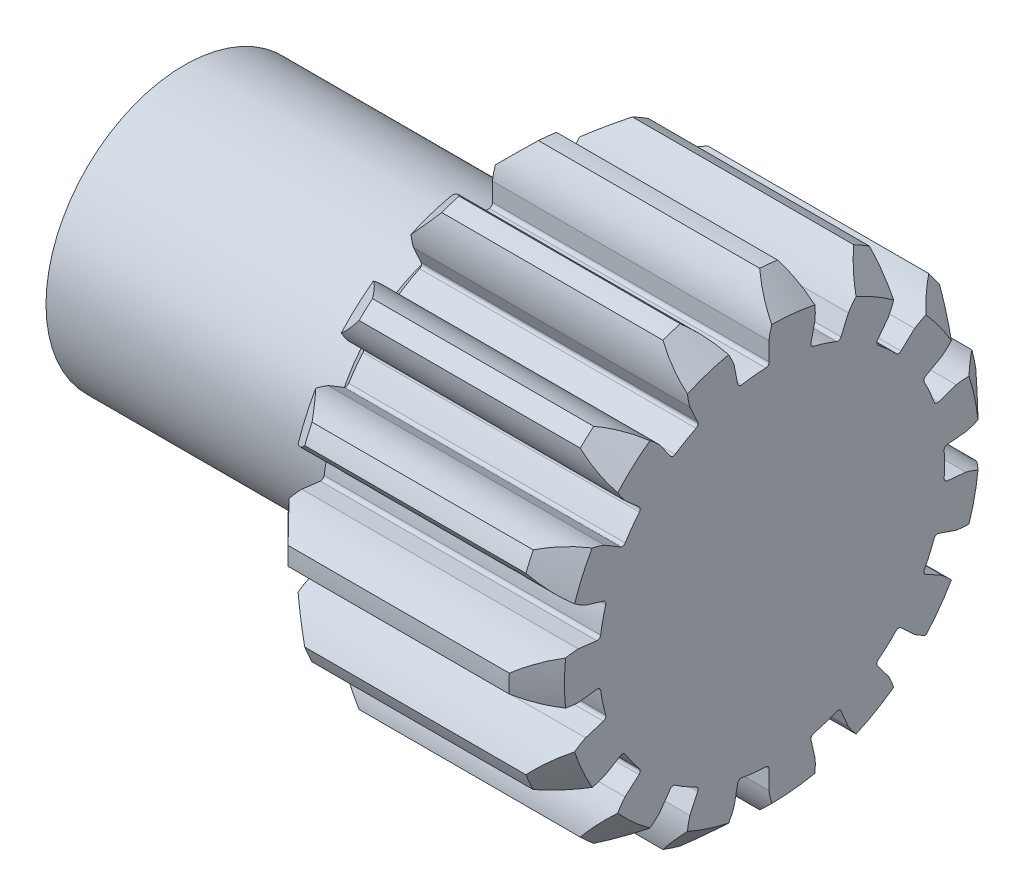
SolidWorks part; units mm, degrees
ref_plane "Спереди" through (0, 0, 0) normal (0, 0, 1) x (1, 0, 0)
ref_plane "Сверху" through (0, 0, 0) normal (0, 1, 0) x (1, 0, 0)
ref_plane "Справа" through (0, 0, 0) normal (1, 0, 0) x (0, 0, -1)
sketch "Эскиз2" plane through (0, 0, 0) normal (1, 0, 0) x (0, 0, -1)
  circle A0 centre (0, 0) radius 5
  dimension "D1" = 10
extrude "Бобышка-Вытянуть2" add sketch "Эскиз2" along normal blind 8
sketch "Эскиз5" plane through (0, 0, 0) normal (-1, 0, 0) x (0, 0, 1)
  circle A0 centre (0, 0) radius 4
  point P3 (0, 0)
  dimension "D1" = 8
extrude "Бобышка-Вытянуть4" add sketch "Эскиз5" along normal blind 9
hole_wizard "Отверстие обработанное метчиком M31" positions "Эскиз6" profile "Эскиз7" tap size "M3" standard "ISO"
sketch "Эскиз6" plane through (-9, 0, 0) normal (-1, 0, 0) x (0, 0, 1)
  point P0 (0, 0)
sketch "Эскиз7" plane through (-9, 0, 0) normal (0, 1, 0) x (0, 0, 1)
  line L0 (0, 0) -> (0, 9.2511)
  line L1 (0, 9.2511) -> (1.25, 8.5)
  line L2 (1.25, 8.5) -> (1.25, 1.25)
  line L3 (1.25, 1.25) -> (2.5, 0)
  line L5 (2.5, 0) -> (0, 0)
  line L6 (-1.25, 1.25) -> (-2.5, 0) construction
  line L10 (0, 9.2511) -> (-1.25, 8.5) construction
  line L11 (0, -6.35) -> (0, 107.95) construction
  dimension "Диаметр сверла" = 2.5
  dimension "Глубина сверла" = 8.5
  dimension "Диаметр передней зенковки" = 5
  dimension "Угол передней зенковки" = 90
  dimension "Угол заточки сверла" = 118
cosmetic thread "Отверстие резьбы1" parameters "D1"=0, "D2"=3.5
ref_plane "Плоскость2" through (4, 0, 0) normal (1, 0, 0) x (0, 0, -1)
sketch "Эскиз9" plane through (4, 0, 0) normal (1, 0, 0) x (0, 0, -1)
  line L0 (0, 0) -> (0, 6) construction
  line L1 (0, 6) -> (1.2298, 6) construction
  line L2 (0, 6) -> (1.9284, 5.2981) construction
  line L3 (0.4492, 6.7851) -> (3.4539, 4.4564) construction
  line L4 (0, 0) -> (-0.084, 5.6375) construction
  line L5 (-0.084, 5.6375) -> (-0.0745, 4.9994)
  line L6 (0, 0) -> (0.7108, 6.7627) construction
  line L7 (1.2543, 5.4969) -> (1.1123, 4.8747)
  arc A0 (0.9713, 6.7303) -> (0.4492, 6.7851) centre (0, 0) ccw
  circle A1 centre (0, 0) radius 6 construction
  circle A2 centre (0, 0) radius 5 construction
  arc A3 (1.1123, 4.8747) -> (-0.0745, 4.9994) centre (0, 0) ccw
  circle A4 centre (0, 0) radius 5.6382 construction
  spline S0 degree 2 poles (-0.084, 5.6375) (0.0098, 6.2791) (0.4492, 6.7851) knots 0 0 0 1 1 1
  spline S1 degree 2 poles (1.2543, 5.4969) (1.296, 6.1439) (0.9713, 6.7303) knots 0 0 0 1 1 1
  point P11 (-0.084, 5.6375)
  dimension "D1" = 12
  dimension "D2" = 13.6
  dimension "D3" = 20
  dimension "D4" = 2.0521
  dimension "D5" = 3.8015
  dimension "D8" = 6
  dimension "D6" = 1.7494
  dimension "D7" = 2.0521
extrude "Бобышка-Вытянуть5" add sketch "Эскиз9" along normal up to surface and the other way up to surface up to face at (8, 0, -5) other way up to face at (0, 0, 4)
fillet "Скругление4" radius 0.1 2 edges at (4, 4.9994, 0.0745) (4, 4.8747, -1.1123)
pattern_circular "Круговой массив1" count 15 over 360 about axis through (8, 0, 0) along (-1, 0, 0) of "Бобышка-Вытянуть5", "Скругление4"
sketch "Эскиз10" plane through (0, 0, 0) normal (0, 0, 1) x (1, 0, 0)
  line L0 (0, 6) -> (8, 6) construction
  line L2 (-9, 0) -> (0, 0) construction
  line L3 (0, 6.8) -> (8, 6.8) construction
  line L4 (0, 6) -> (0, 6.8)
  line L5 (0, 6.8) -> (0.8, 6.8)
  line L6 (0.8, 6.8) -> (0, 6)
  line L7 (4, 6.8) -> (4, 0) construction
  line L8 (8, 0) -> (0, 0) construction
  line L9 (8, 6) -> (8, 6.8)
  line L10 (8, 6.8) -> (7.2, 6.8)
  line L11 (7.2, 6.8) -> (8, 6)
  line L13 (0, 6.7851) -> (0, 5.6375) construction
  line L14 (8, 5.6375) -> (8, 6.7851) construction
  point P3 (0, 0)
  point P4 (0.0509, 6)
  dimension "D1" = 6
  dimension "D3" = 6.8
revolve "Вырез-Повернуть2" cut sketch "Эскиз10" angle 360 about axis through (-9, 0, 0) along (1, 0, 0)
sketch "Эскиз11" plane through (0, 0, 0) normal (0, 0, 1) x (1, 0, 0)
  line L0 (0, 4) -> (0, 3.7)
  line L1 (0, 3.7) -> (-0.5, 3.7)
  line L2 (-0.5, 3.7) -> (-0.8, 4)
  line L3 (0, 4) -> (-9, 4) construction
  line L4 (-0.8, 4) -> (0, 4)
  point P4 (-0.5011, 3.7)
  dimension "D1" = 0.3
  dimension "D2" = 0.8
  dimension "D3" = 45
revolve "Вырез-Повернуть3" cut sketch "Эскиз11" angle 360 about axis through (-9, 0, 0) along (1, 0, 0)
fillet "Скругление5" radius 0.2 2 edges at (-0.5, 0, 3.7) (0, 0, 3.7)
equation "\"Модуль\"= 0.8мм"
equation "\"Число2\"= 15"
equation "\"D1@Эскиз2\"= \"Модуль\" * (\"Число2\" - 2.5)"
equation "\"D1@Эскиз9\"= \"Модуль\" * \"Число2\""
equation "\"D2@Эскиз9\"= \"Модуль\" * (\"Число2\" + 2)"
equation "\"D6@Эскиз9\"= \"D5@Эскиз9\" - \"D4@Эскиз9\""
equation "\"D7@Эскиз9\"= \"D4@Эскиз9\""
equation "\"D8@Эскиз9\"= 90 / \"Число2\""
equation "\"D1@Эскиз10\"=\"Модуль\" * \"Число2\" / 2"
equation "\"D3@Эскиз10\"= \"Модуль\" * (\"Число2\" + 2) / 2"
